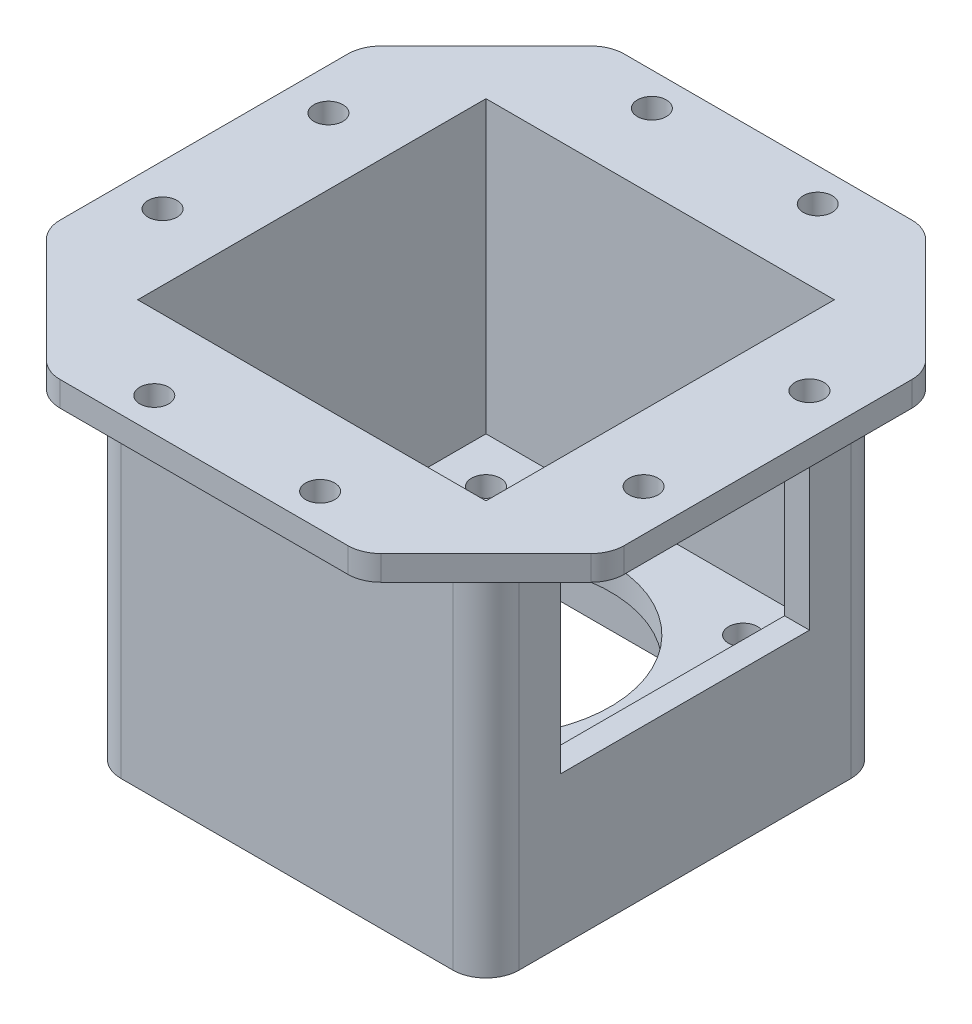
SolidWorks part; units mm, degrees
ref_plane "Front Plane" through (0, 0, 0) normal (0, 0, 1) x (1, 0, 0)
ref_plane "Top Plane" through (0, 0, 0) normal (0, 1, 0) x (1, 0, 0)
ref_plane "Right Plane" through (0, 0, 0) normal (1, 0, 0) x (0, 0, -1)
sketch "Sketch2" plane through (0, 0, 0) normal (0, 1, 0) x (1, 0, 0)
  line L0 (-24, 24) -> (24, 24)
  line L1 (-21, 21) -> (21, 21) construction
  line L2 (-21, 21) -> (-21, -21) construction
  line L3 (-21, -21) -> (21, -21) construction
  line L4 (21, 21) -> (21, -21) construction
  line L5 (-21, 21) -> (21, -21) construction
  line L6 (-21, -21) -> (21, 21) construction
  line L7 (24, 24) -> (24, -24)
  line L8 (-24, -24) -> (24, -24)
  line L9 (-24, 24) -> (-24, -24)
  line L10 (-15.5, 15.5) -> (15.5, 15.5) construction
  line L11 (-15.5, 15.5) -> (-15.5, -15.5) construction
  line L12 (-15.5, -15.5) -> (15.5, -15.5) construction
  line L13 (15.5, -15.5) -> (15.5, 15.5) construction
  circle A0 centre (0, 0) radius 15
  circle A1 centre (-15.5, 15.5) radius 1.75
  circle A2 centre (15.5, 15.5) radius 1.75
  circle A3 centre (15.5, -15.5) radius 1.75
  circle A4 centre (-15.5, -15.5) radius 1.75
  point P0 (0, 0)
  dimension "D3" = 30
  dimension "D4" = 3.5
  dimension "D1" = 42
  dimension "D2" = 3
  dimension "D5" = 31
extrude "Boss-Extrude1" add sketch "Sketch2" along normal blind 3
sketch "Sketch3" plane through (0, 3, 0) normal (0, 1, 0) x (1, 0, 0)
  line L1 (-21, -21) -> (21, -21)
  line L2 (-21, -21) -> (-21, 21)
  line L3 (-21, 21) -> (21, 21)
  line L4 (21, -21) -> (21, 21)
  line L5 (-21, -21) -> (21, 21) construction
  line L6 (-21, 21) -> (21, -21) construction
  line L7 (-24, -24) -> (24, -24)
  line L8 (-24, -24) -> (-24, 24)
  line L9 (-24, 24) -> (24, 24)
  line L10 (24, -24) -> (24, 24)
  line L11 (-24, -24) -> (24, 24) construction
  line L12 (-24, 24) -> (24, -24) construction
  point P0 (0, 0)
  point P5 (0, 0)
  dimension "D1" = 42
extrude "Boss-Extrude2" add sketch "Sketch3" along normal blind 32
sketch "Sketch4" plane through (0, 35, 0) normal (0, 1, 0) x (1, 0, 0)
  line L1 (-21, -21) -> (21, -21)
  line L2 (-21, -21) -> (-21, 21)
  line L3 (-21, 21) -> (21, 21)
  line L4 (21, -21) -> (21, 21)
  line L5 (-21, -21) -> (21, 21) construction
  line L6 (-21, 21) -> (21, -21) construction
  line L23 (-34, 0) -> (34, 0) construction
  line L24 (-34, 10) -> (34, 10) construction
  line L44 (-34, -10) -> (34, -10) construction
  line L45 (0, -34) -> (0, 34) construction
  line L46 (34, -34) -> (34, 34)
  line L47 (34, 34) -> (-34, 34)
  line L48 (-34, 34) -> (-34, -34)
  line L49 (-34, -34) -> (34, -34)
  line L50 (34, -34) -> (34, 34)
  line L51 (34, 34) -> (-34, 34)
  line L52 (-34, 34) -> (-34, -34)
  line L53 (-34, -34) -> (34, -34)
  line L54 (-10, 34) -> (-10, -34) construction
  line L55 (10, 34) -> (10, -34) construction
  line L56 (-34, 30) -> (34, 30) construction
  line L57 (-29, 10) -> (-29, -10) construction
  line L58 (29, 10) -> (29, -10) construction
  line L59 (-34, -30) -> (34, -30) construction
  circle A0 centre (-10, 30) radius 1.75
  circle A1 centre (10, 30) radius 1.75
  circle A2 centre (-29, 10) radius 1.75
  circle A3 centre (-29, -10) radius 1.75
  circle A4 centre (-10, -30) radius 1.75
  circle A5 centre (10, -30) radius 1.75
  circle A6 centre (29, -10) radius 1.75
  circle A7 centre (29, 10) radius 1.75
  point P0 (0, 0)
  dimension "D6" = 3.5
  dimension "D7" = 3.5
  dimension "D9" = 3.5
  dimension "D1" = 10
  dimension "D2" = 10
  dimension "D3" = 10
  dimension "D4" = 10
  dimension "D5" = 10
  dimension "D8" = 20
  dimension "D10" = 20
  dimension "D11" = 5
  dimension "D12" = 5
extrude "Boss-Extrude3" add sketch "Sketch4" along normal blind 3
chamfer "Chamfer1" distance 15 angle 45 4 edges at (34, 36.5, 34) (34, 36.5, -34) (-34, 36.5, -34) (-34, 36.5, 34)
sketch "Sketch5" plane through (0, 0, 0) normal (0, -1, 0) x (1, 0, 0)
  line L1 (-21, 21) -> (21, 21)
  line L2 (-21, 21) -> (-21, -21)
  line L3 (-21, -21) -> (21, -21)
  line L4 (21, 21) -> (21, -21)
  line L5 (-21, 21) -> (21, -21) construction
  line L6 (-21, -21) -> (21, 21) construction
  line L7 (-24, -24) -> (24, -24)
  line L8 (-24, -24) -> (-24, 24)
  line L9 (-24, 24) -> (24, 24)
  line L10 (24, -24) -> (24, 24)
  line L11 (-24, -24) -> (24, 24) construction
  line L12 (-24, 24) -> (24, -24) construction
  line L13 (24, -24) -> (-24, -24) construction
  point P0 (0, 0)
  point P5 (0, 0)
  dimension "D1" = 42
extrude "Boss-Extrude4" add sketch "Sketch5" along normal blind 10
fillet "Fillet1" radius 4 4 edges at (-24, 12.5, 24) (-24, 12.5, -24) (24, 12.5, 24) (24, 12.5, -24)
sketch "Sketch7" plane through (24, 0, 0) normal (1, 0, 0) x (0, 0, -1)
  line L0 (21, 0) -> (-21, 0) construction
  line L1 (-15, 28) -> (15, 28)
  line L2 (-15, 28) -> (-15, 8)
  line L3 (-15, 8) -> (15, 8)
  line L4 (15, 28) -> (15, 8)
  line L5 (-15, 28) -> (15, 8) construction
  line L6 (-15, 8) -> (15, 28) construction
  point P0 (0, 18)
  dimension "D1" = 20
  dimension "D2" = 30
  dimension "D3" = 28
extrude "Cut-Extrude2" cut sketch "Sketch7" against normal up to next
fillet "Fillet2" radius 4 8 edges at (-19, 36.5, 34) (-34, 36.5, 19) (-34, 36.5, -19) (-19, 36.5, -34) (19, 36.5, -34) (34, 36.5, -19) (19, 36.5, 34) (34, 36.5, 19)
